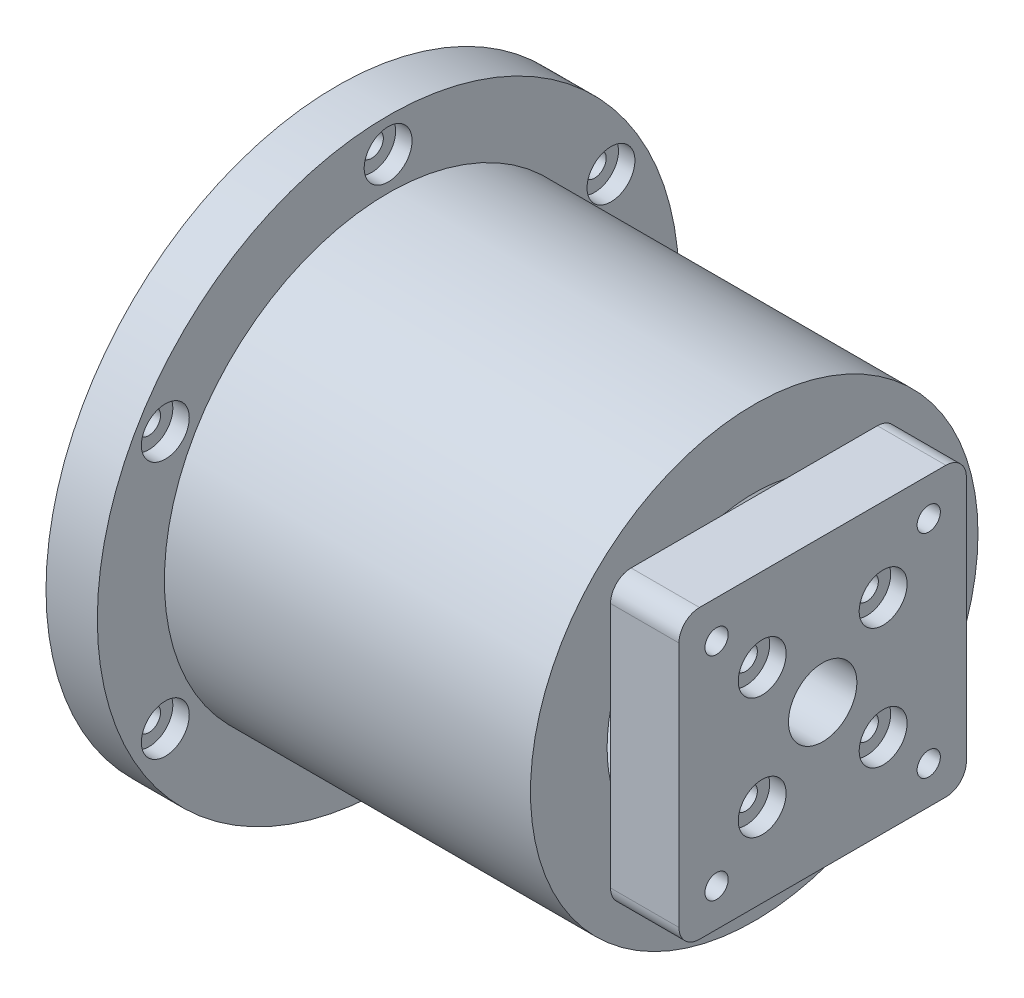
SolidWorks part; units mm, degrees
material "7075-O (SS)"
ref_plane "Front" through (0, 0, 0) normal (0, 0, 1) x (1, 0, 0)
ref_plane "Top" through (0, 0, 0) normal (0, 1, 0) x (1, 0, 0)
ref_plane "Right" through (0, 0, 0) normal (1, 0, 0) x (0, 0, -1)
sketch "Croquis1" plane through (0, 0, 0) normal (1, 0, 0) x (0, 0, -1)
  line L6 (-18, -21) -> (18, -21)
  line L14 (-21, -18) -> (-21, 18)
  line L15 (-18, 21) -> (18, 21)
  line L16 (21, -18) -> (21, 18)
  line L17 (-21, -21) -> (21, 21) construction
  line L18 (-21, 21) -> (21, -21) construction
  circle A0 centre (0, 0) radius 5
  arc A1 (18, -21) -> (21, -18) centre (18, -18) ccw
  arc A2 (-18, -21) -> (-21, -18) centre (-18, -18) cw
  arc A3 (-21, 18) -> (-18, 21) centre (-18, 18) cw
  arc A4 (18, 21) -> (21, 18) centre (18, 18) cw
  point P0 (0, 0)
  dimension "D4" = 10
  dimension "D2" = 3
  dimension "D1" = 42
extrude "Saliente-Extruir1" add sketch "Croquis1" along normal blind 10
sketch "Croquis2" plane through (0, 0, 0) normal (-1, 0, 0) x (0, 0, 1)
  circle A0 centre (0, 0) radius 32.7
  dimension "D1" = 65.4
extrude "Saliente-Extruir2" add sketch "Croquis2" along normal blind 53.5 from surface contours A0 starting at plane "Right"
sketch "Croquis3" plane through (-53.5, 0, 0) normal (-1, 0, 0) x (0, 0, 1)
  circle A0 centre (0, 0) radius 21.5
  dimension "D1" = 43
extrude "Cortar-Extruir2" cut sketch "Croquis3" against normal up to surface (53.5 mm away) contours A0 up to face at (0, 0, 0)
hole_wizard "Refrentado para tornillo con cabeza troncocónica de M31" positions "Croquis4" profile "Croquis6" counterbore size "M3" standard "Ansi Metric" end condition up to next
sketch "Croquis4" plane through (10, 0, 0) normal (1, 0, 0) x (0, 0, -1)
  line L0 (0, 0) -> (-8.8388, 8.8388) construction
  line L3 (0, 50) -> (0, -50) construction
  point P0 (-8.8388, 8.8388)
  point P16 (8.8388, 8.8388)
  point P17 (8.8388, -8.8388)
  point P18 (-8.8388, -8.8388)
  dimension "D1" = 45
  dimension "D2" = 12.5
  dimension "D3" = 4
sketch "Croquis6" plane through (10, 8.8388, 8.8388) normal (0, 1, 0) x (0, 0, -1)
  line L0 (0, 0) -> (0, 10)
  line L1 (0, 10) -> (1.7, 10)
  line L3 (1.7, 10) -> (1.7, 2.4)
  line L4 (1.7, 2.4) -> (3.5, 2.4)
  line L5 (3.5, 2.4) -> (3.5, 0)
  line L7 (3.5, 0) -> (0, 0)
  line L11 (0, -6.35) -> (0, 107.95) construction
  dimension "Diámetro de taladro hasta el siguiente" = 3.4
  dimension "Profundidad de taladro hasta el siguiente" = 10
  dimension "Diámetro de refrentado" = 7
  dimension "Profundidad de refrentado" = 2.4
hole_wizard "Taladro de margen para M31" positions "Croquis7" profile "Croquis9" hole size "M3" standard "Ansi Metric"
sketch "Croquis7" plane through (10, 0, 0) normal (1, 0, 0) x (0, 0, -1)
  line L0 (0, 0) -> (15.5, 15.5) construction
  line L3 (0, 50) -> (0, -50) construction
  line L4 (50, 0) -> (-50, 0) construction
  point P0 (15.5, 15.5)
  point P17 (15.5, -15.5)
  point P18 (-15.5, -15.5)
  point P19 (-15.5, 15.5)
  dimension "D1" = 45
  dimension "D2" = 15.5
  dimension "D3" = 4
sketch "Croquis9" plane through (10, 15.5, -15.5) normal (0, 1, 0) x (0, 0, -1)
  line L0 (0, 0) -> (0, 17.0215)
  line L1 (0, 17.0215) -> (1.7, 16)
  line L2 (1.7, 16) -> (1.7, 0)
  line L5 (1.7, 0) -> (0, 0)
  line L10 (0, 17.0215) -> (-1.7, 16) construction
  line L11 (0, -6.35) -> (0, 107.95) construction
  dimension "Diámetro de taladro" = 3.4
  dimension "Profundidad de taladro" = 16
  dimension "Ángulo de perforador" = 118
sketch "Croquis11" plane through (-53.5, 0, 0) normal (-1, 0, 0) x (0, 0, 1)
  line L6 (-18.5, -21.5) -> (18.5, -21.5)
  line L14 (-21.5, -18.5) -> (-21.5, 18.5)
  line L15 (-18.5, 21.5) -> (18.5, 21.5)
  line L16 (21.5, -18.5) -> (21.5, 18.5)
  line L17 (-21.5, -21.5) -> (21.5, 21.5) construction
  line L18 (-21.5, 21.5) -> (21.5, -21.5) construction
  circle A0 centre (0, 0) radius 42.5
  arc A1 (-18.5, -21.5) -> (-21.5, -18.5) centre (-18.5, -18.5) cw
  arc A2 (18.5, -21.5) -> (21.5, -18.5) centre (18.5, -18.5) ccw
  arc A3 (18.5, 21.5) -> (21.5, 18.5) centre (18.5, 18.5) cw
  arc A4 (-21.5, 18.5) -> (-18.5, 21.5) centre (-18.5, 18.5) cw
  circle A5 centre (0, 0) radius 21.5 construction
  dimension "D1" = 85
  dimension "D3" = 3
extrude "Saliente-Extruir3" add sketch "Croquis11" along normal blind 7.5
hole_wizard "Taladro de margen para M32" positions "Croquis12" profile "Croquis13" hole size "M3" standard "Ansi Metric"
sketch "Croquis12" plane through (-53.5, 0, 0) normal (-1, 0, 0) x (0, 0, 1)
  line L0 (0, 0) -> (-17.075, 17.075) construction
  line L3 (0, -50) -> (0, 50) construction
  line L4 (50, 0) -> (-50, 0) construction
  point P0 (-17.075, 17.075)
  point P18 (17.075, 17.075)
  point P19 (17.075, -17.075)
  point P20 (-17.075, -17.075)
  dimension "D1" = 45
  dimension "D2" = 17.075
  dimension "D3" = 4
sketch "Croquis13" plane through (-53.5, 17.075, -17.075) normal (0, 1, 0) x (0, 0, 1)
  line L0 (0, 0) -> (0, 17.0215)
  line L1 (0, 17.0215) -> (1.7, 16)
  line L2 (1.7, 16) -> (1.7, 0)
  line L5 (1.7, 0) -> (0, 0)
  line L10 (0, 17.0215) -> (-1.7, 16) construction
  line L11 (0, -6.35) -> (0, 107.95) construction
  dimension "Diámetro de taladro" = 3.4
  dimension "Profundidad de taladro" = 16
  dimension "Ángulo de perforador" = 118
hole_wizard "Refrentado para tornillo con cabeza troncocónica de M32" positions "Croquis14" profile "Croquis16" counterbore size "M3" standard "Ansi Metric" end condition up to next
sketch "Croquis14" plane through (-53.5, 0, 0) normal (1, 0, 0) x (0, 0, -1)
  line L0 (0, 50) -> (0, -50) construction
  line L1 (0, 42.5) -> (0, 32.7) construction
  circle A0 centre (0, 0) radius 42.5 construction
  circle A1 centre (0, 0) radius 32.7 construction
  point P0 (0, 37.6)
  point P15 (0, 37.6)
  point P20 (32.5626, 18.8)
  point P21 (32.5626, -18.8)
  point P22 (0, -37.6)
  point P23 (-32.5626, -18.8)
  point P24 (-32.5626, 18.8)
  dimension "D1" = 6
sketch "Croquis16" plane through (-53.5, 37.6, 0) normal (0, 1, 0) x (0, 0, -1)
  line L0 (0, 0) -> (0, 7.5)
  line L1 (0, 7.5) -> (1.7, 7.5)
  line L3 (1.7, 7.5) -> (1.7, 2.4)
  line L4 (1.7, 2.4) -> (3.5, 2.4)
  line L5 (3.5, 2.4) -> (3.5, 0)
  line L7 (3.5, 0) -> (0, 0)
  line L11 (0, -6.35) -> (0, 107.95) construction
  dimension "Diámetro de taladro hasta el siguiente" = 3.4
  dimension "Profundidad de taladro hasta el siguiente" = 7.5
  dimension "Diámetro de refrentado" = 7
  dimension "Profundidad de refrentado" = 2.4
